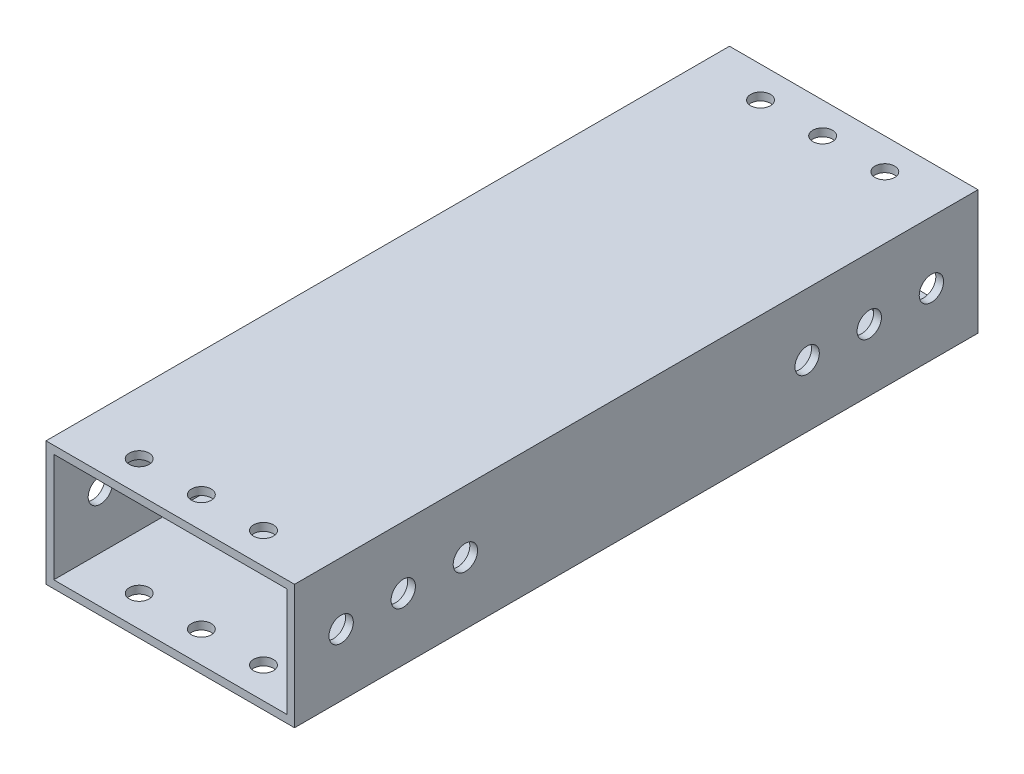
SolidWorks part; units mm, degrees
material "6061-T6 (SS)"
ref_plane "Front Plane" through (0, 0, 0) normal (0, 0, 1) x (1, 0, 0)
ref_plane "Top Plane" through (0, 0, 0) normal (0, 1, 0) x (1, 0, 0)
ref_plane "Right Plane" through (0, 0, 0) normal (1, 0, 0) x (0, 0, -1)
sketch "Sketch1" plane through (0, 0, 0) normal (0, 0, 1) x (1, 0, 0)
  line L0 (-23.8125, 11.1125) -> (23.8125, 11.1125)
  line L1 (-25.4, -12.7) -> (25.4, -12.7)
  line L2 (-25.4, -12.7) -> (-25.4, 12.7)
  line L3 (-25.4, 12.7) -> (25.4, 12.7)
  line L4 (25.4, -12.7) -> (25.4, 12.7)
  line L5 (-25.4, -12.7) -> (25.4, 12.7) construction
  line L6 (-25.4, 12.7) -> (25.4, -12.7) construction
  line L7 (23.8125, -11.1125) -> (23.8125, 11.1125)
  line L8 (-23.8125, -11.1125) -> (23.8125, -11.1125)
  line L9 (-23.8125, -11.1125) -> (-23.8125, 11.1125)
  point P0 (0, 0)
  dimension "D1" = 50.8
  dimension "D2" = 25.4
  dimension "D3" = 1.5875
extrude "Boss-Extrude1" add sketch "Sketch1" along normal mid plane 139.7
sketch "Sketch2" plane through (0, 12.7, 0) normal (0, 1, 0) x (1, 0, 0)
  line L0 (25.4, 69.85) -> (-25.4, 69.85) construction
  line L1 (25.4, 0) -> (-25.4, 0) construction
  line L2 (25.4, -69.85) -> (25.4, 69.85) construction
  line L3 (-25.4, -69.85) -> (-25.4, 69.85) construction
  circle A0 centre (-12.7, 63.5) radius 2.0193
  circle A1 centre (0, 63.5) radius 2.0193
  circle A2 centre (12.7, 63.5) radius 2.0193
  circle A3 centre (12.7, -63.5) radius 2.0193
  circle A4 centre (0, -63.5) radius 2.0193
  circle A5 centre (-12.7, -63.5) radius 2.0193
  dimension "D1" = 4.0386
  dimension "D2" = 12.7
  dimension "D3" = 12.7
  dimension "D4" = 6.35
extrude "Cut-Extrude1" cut sketch "Sketch2" against normal through all
sketch "Sketch3" plane through (25.4, 0, 0) normal (1, 0, 0) x (0, 0, -1)
  line L0 (0, 12.7) -> (0, -12.7) construction
  line L1 (-69.85, 12.7) -> (69.85, 12.7) construction
  line L2 (-69.85, -12.7) -> (69.85, -12.7) construction
  line L3 (-69.85, -12.7) -> (-69.85, 12.7) construction
  circle A0 centre (-60.325, 0) radius 2.4892
  circle A1 centre (60.325, 0) radius 2.4892
  circle A2 centre (-47.625, 0) radius 2.4892
  circle A3 centre (-34.925, 0) radius 2.4892
  circle A4 centre (34.925, 0) radius 2.4892
  circle A5 centre (47.625, 0) radius 2.4892
  dimension "D3" = 4.9784
  dimension "D2" = 9.525
  dimension "D4" = 12.7
  dimension "D5" = 12.7
extrude "Cut-Extrude2" cut sketch "Sketch3" against normal through all
